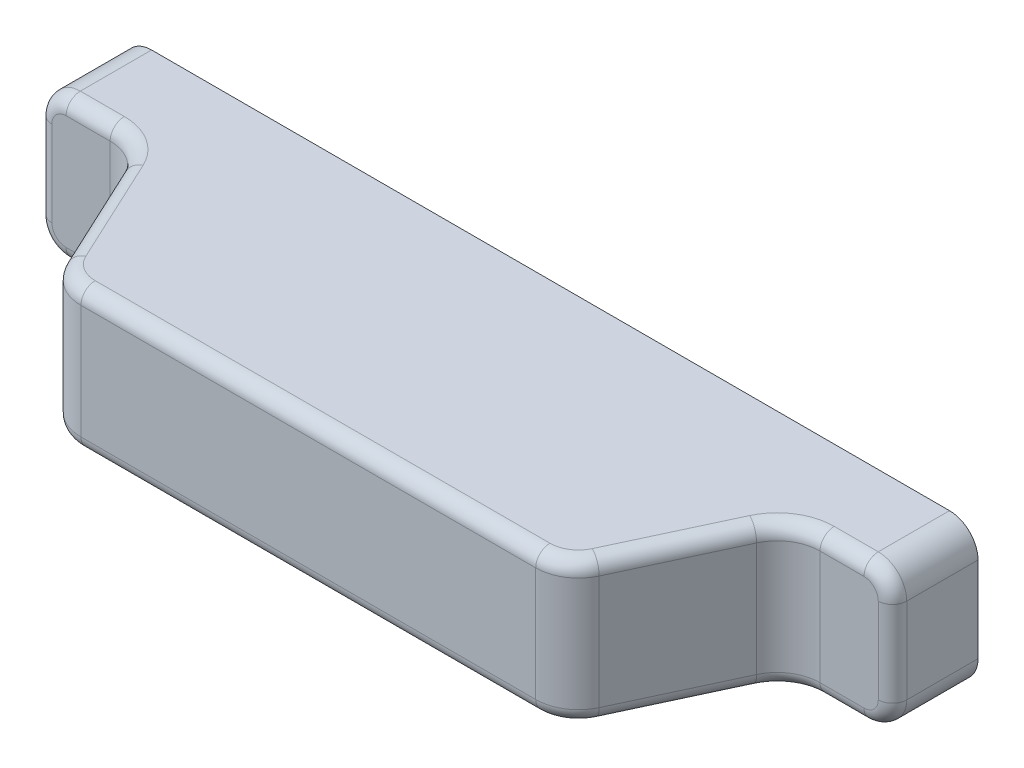
SolidWorks part; units mm, degrees
ref_plane "Front Plane" through (0, 0, 0) normal (0, 0, 1) x (1, 0, 0)
ref_plane "Top Plane" through (0, 0, 0) normal (0, 1, 0) x (1, 0, 0)
ref_plane "Right Plane" through (0, 0, 0) normal (1, 0, 0) x (0, 0, -1)
sketch "Sketch1" plane through (0, 0, 0) normal (0, 0, 1) x (1, 0, 0)
  line L1 (-119, -97.7573) -> (-59, -97.7573)
  line L2 (-119, -97.7573) -> (-119, -87.7573)
  line L3 (-119, -87.7573) -> (-59, -87.7573)
  line L4 (-59, -97.7573) -> (-59, -87.7573)
  line L7 (-89, -7.4927) -> (-89, -172.4927) construction
  dimension "D1" = 30
  dimension "D2" = 60
extrude "Boss-Extrude1" add sketch "Sketch1" along normal blind 17
sketch "Sketch2" plane through (0, -97.7573, 0) normal (0, -1, 0) x (1, 0, 0)
  line L0 (-106.8706, 17) -> (-112, 6)
  line L1 (-119, 17) -> (-59, 17) construction
  line L2 (-112, 6) -> (-119, 6)
  line L3 (-119, 17) -> (-119, 0) construction
  line L4 (-119, 0) -> (-59, 0) construction
  line L5 (-119, 6) -> (-119, 17)
  line L6 (-119, 17) -> (-106.8706, 17)
  line L7 (-89, 0) -> (-89, 17) construction
  line L8 (-104, 17) -> (-74, 17) construction
  line L9 (-59, 17) -> (-71.1294, 17)
  line L10 (-59, 6) -> (-59, 17)
  line L11 (-66, 6) -> (-59, 6)
  line L12 (-71.1294, 17) -> (-66, 6)
  dimension "D1" = 6
  dimension "D2" = 7
  dimension "D3" = 115
extrude "Cut-Extrude1" cut sketch "Sketch2" against normal up to surface (10 mm away) up to face at (-89, -87.7573, 8.5)
fillet "Fillet1" radius 3 4 edges at (-66, -92.7573, 6) (-71.1294, -92.7573, 17) (-106.8706, -92.7573, 17) (-112, -92.7573, 6)
fillet "Fillet2" radius 2 4 edges at (-119, -87.7573, 3) (-119, -97.7573, 3) (-59, -87.7573, 3) (-59, -97.7573, 3)
fillet "Fillet3" radius 1 24 edges at (-71.4287, -97.7573, 16.5302) (-89, -97.7573, 17) (-106.5713, -97.7573, 16.5302) (-109.4353, -97.7573, 11.5) (-112.2993, -97.7573, 6.4698) (-115.4556, -97.7573, 6) (-118.4142, -97.1715, 6) (-119, -92.7573, 6) (-118.4142, -88.3431, 6) (-115.4556, -87.7573, 6) (-112.2993, -87.7573, 6.4698) (-109.4353, -87.7573, 11.5) (-106.5713, -87.7573, 16.5302) (-89, -87.7573, 17) (-71.4287, -87.7573, 16.5302) (-68.5647, -87.7573, 11.5) (-65.7007, -87.7573, 6.4698) (-62.5444, -87.7573, 6) (-59.5858, -88.3431, 6) (-59, -92.7573, 6) (-59.5858, -97.1715, 6) (-62.5444, -97.7573, 6) (-65.7007, -97.7573, 6.4698) (-68.5647, -97.7573, 11.5)
